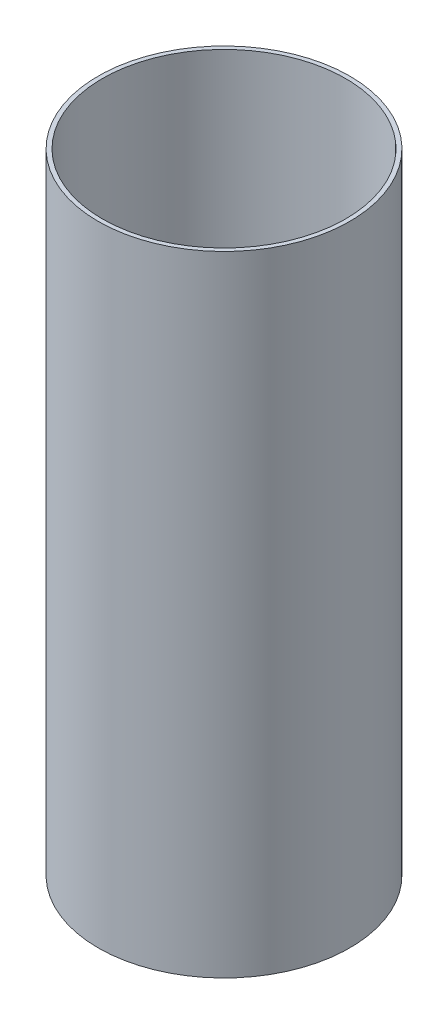
SolidWorks part; units mm, degrees
ref_plane "Front Plane" through (0, 0, 0) normal (0, 0, 1) x (1, 0, 0)
ref_plane "Top Plane" through (0, 0, 0) normal (0, 1, 0) x (1, 0, 0)
ref_plane "Right Plane" through (0, 0, 0) normal (1, 0, 0) x (0, 0, -1)
sketch "Sketch1" plane through (0, 0, 0) normal (0, 1, 0) x (1, 0, 0)
  circle A0 centre (0, 0) radius 58
  circle A1 centre (0, 0) radius 60
  dimension "D1" = 2
  dimension "D2" = 120
extrude "Boss-Extrude1" add sketch "Sketch1" along normal blind 300
